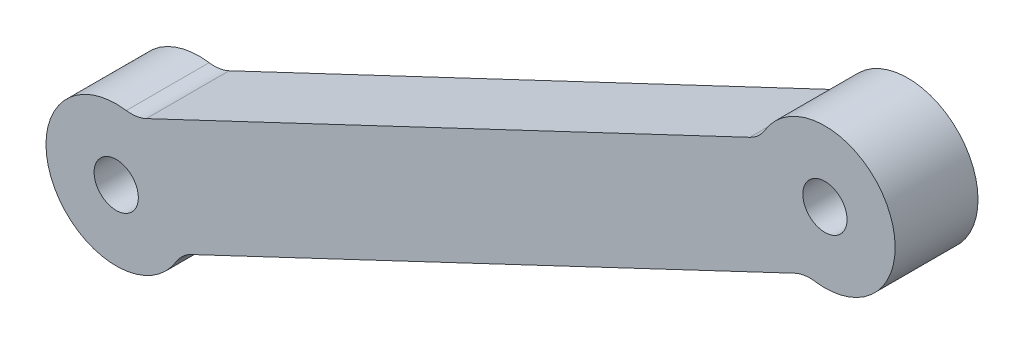
SolidWorks part; units mm, degrees
ref_plane "Front Plane" through (0, 0, 0) normal (0, 0, 1) x (1, 0, 0)
ref_plane "Top Plane" through (0, 0, 0) normal (0, 1, 0) x (1, 0, 0)
ref_plane "Right Plane" through (0, 0, 0) normal (1, 0, 0) x (0, 0, -1)
sketch "Sketch1" plane through (0, 0, 0) normal (0, 0, 1) x (1, 0, 0)
  line L1 (173.2391, 87.8282) -> (216.9022, 108.4876)
  line L2 (169.9801, 94.7161) -> (213.6432, 115.3755)
  circle A0 centre (219.0801, 113.733) radius 1.6
  circle A1 centre (167.8022, 89.4706) radius 1.6
  arc A2 (168.5299, 94.4982) -> (172.151, 86.845) centre (167.8022, 89.4706) ccw
  arc A3 (218.3524, 108.7054) -> (214.7313, 116.3586) centre (219.0801, 113.733) ccw
  arc A4 (213.6432, 115.3755) -> (214.7313, 116.3586) centre (212.5568, 117.6714) ccw
  arc A5 (216.9022, 108.4876) -> (218.3524, 108.7054) centre (217.9886, 106.1916) cw
  arc A6 (169.9801, 94.7161) -> (168.5299, 94.4982) centre (168.8937, 97.012) cw
  arc A7 (172.151, 86.845) -> (173.2391, 87.8282) centre (174.3255, 85.5322) cw
  dimension "D1" = 2.54
  dimension "D2" = 2.54
  dimension "D3" = 2.54
  dimension "D4" = 2.54
extrude "Boss-Extrude1" add sketch "Sketch1" along normal blind 5.9944
